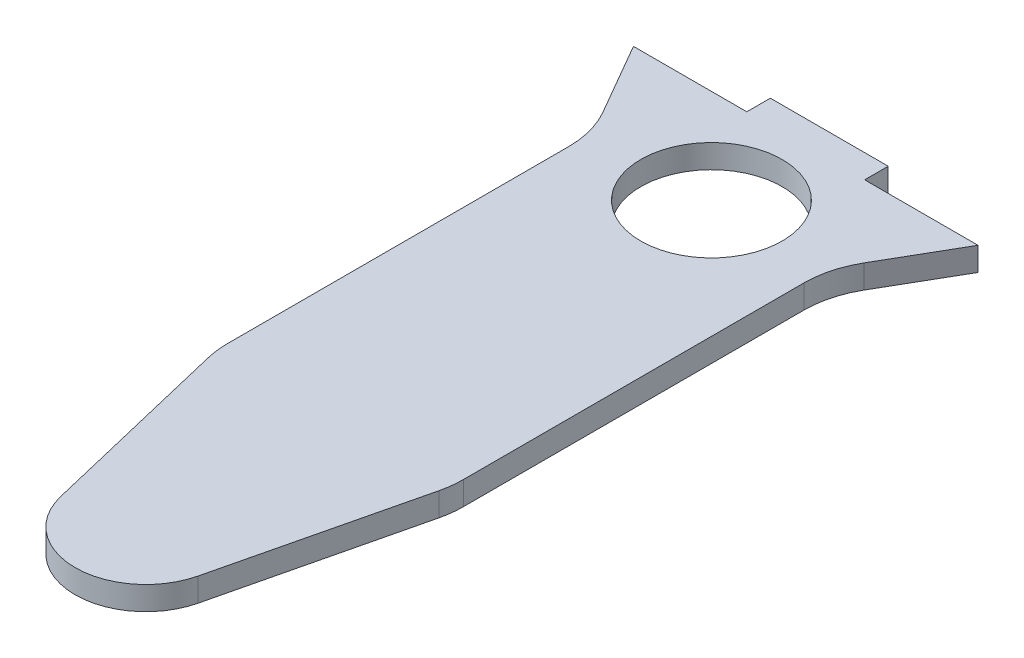
SolidWorks part; units mm, degrees
material "Pine"
ref_plane "Front Plane" through (0, 0, 0) normal (0, 0, 1) x (1, 0, 0)
ref_plane "Top Plane" through (0, 0, 0) normal (0, 1, 0) x (1, 0, 0)
ref_plane "Right Plane" through (0, 0, 0) normal (1, 0, 0) x (0, 0, -1)
sketch "Sketch2" plane through (0, 69.85, 0) normal (0, 1, 0) x (1, 0, 0)
  line L0 (-103.1875, 0) -> (103.1875, 0) construction
  line L1 (-15.875, 6.35) -> (15.875, 6.35)
  line L4 (15.875, 6.35) -> (15.875, 0)
  line L6 (31.75, -127) -> (31.75, -32.2059)
  line L10 (-15.875, 0) -> (-46.4147, 0)
  line L13 (46.4147, 0) -> (35.153, -19.5059)
  line L15 (0, 0) -> (0, -193.7253) construction
  line L16 (46.4147, 0) -> (15.875, 0)
  line L19 (-31.75, -127) -> (-31.75, -32.2059)
  line L20 (-46.4147, 0) -> (-35.153, -19.5059)
  line L23 (-15.875, 6.35) -> (-15.875, 0)
  line L25 (18.5265, -182.2353) -> (31.75, -127)
  line L27 (-18.5265, -182.2353) -> (-31.75, -127)
  arc A0 (-18.5265, -182.2353) -> (18.5265, -182.2353) centre (0, -177.8) ccw
  arc A3 (35.153, -19.5059) -> (31.75, -32.2059) centre (57.15, -32.2059) ccw
  arc A5 (-35.153, -19.5059) -> (-31.75, -32.2059) centre (-57.15, -32.2059) cw
  circle A6 centre (0, -25.4) radius 19.05
  point P15 (31.75, -25.4)
  dimension "D1" = 38.1
  dimension "D3" = 25.4
  dimension "D5" = 127
  dimension "D7" = 38.1
  dimension "D2" = 177.8
  dimension "D4" = 63.5
  dimension "D6" = 25.4
  dimension "D8" = 25.4
  dimension "D9" = 120
extrude "Boss-Extrude1" add sketch "Sketch2" along normal blind 6.35
fillet "Fillet1" radius 25.4 2 edges at (31.75, 73.025, 127) (-31.75, 73.025, 127)
